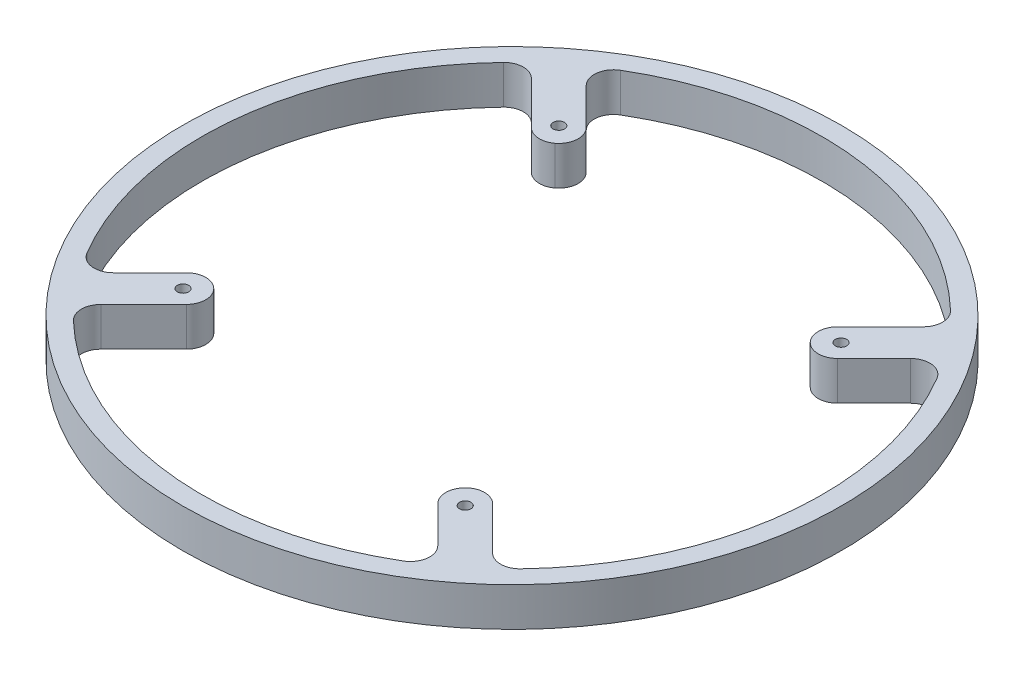
SolidWorks part; units mm, degrees
material "6061-T6 (SS)"
ref_plane "Front Plane" through (0, 0, 0) normal (0, 0, 1) x (1, 0, 0)
ref_plane "Top Plane" through (0, 0, 0) normal (0, 1, 0) x (1, 0, 0)
ref_plane "Right Plane" through (0, 0, 0) normal (1, 0, 0) x (0, 0, -1)
sketch "Sketch2" plane through (0, 0, 0) normal (1, 0, 0) x (0, 0, -1)
  line L0 (-55, 0) -> (-84.9998, 0)
  line L1 (-84.9998, 0) -> (-84.9998, 10)
  line L2 (-84.9998, 10) -> (-55, 10)
  line L5 (-55, 10) -> (-55, 0)
  dimension "D1" = 84.9998
  dimension "D2" = 10
  dimension "D3" = 55
ref_axis "Axis1" through (0, 3.6789, 0) along (0, 1, 0)
revolve "Revolve1" add sketch "Sketch2" angle 360 about axis through (0, 3.6789, 0) along (0, 1, 0)
sketch "Sketch9" plane through (0, 0, 0) normal (0, 1, 0) x (1, 0, 0)
  line L1 (42.4264, -42.4264) -> (-42.4264, -42.4264) construction
  line L2 (42.4264, -42.4264) -> (42.4264, 42.4264) construction
  line L3 (42.4264, 42.4264) -> (-42.4264, 42.4264) construction
  line L4 (-42.4264, -42.4264) -> (-42.4264, 42.4264) construction
  line L5 (0, 0) -> (0, 27.9091) construction
  line L7 (0, 0) -> (26.5726, 0) construction
  line L11 (-43.4619, 48.4619) -> (-36.3909, 55.533) construction
  line L12 (-43.4619, 48.4619) -> (-36.3909, 41.3909) construction
  line L13 (-36.3909, 55.533) -> (-29.3198, 48.4619) construction
  line L16 (-36.3909, 41.3909) -> (-36.3909, 55.533) construction
  line L18 (-43.4619, 48.4619) -> (-29.3198, 48.4619) construction
  line L20 (-29.3198, 48.4619) -> (-36.3909, 41.3909) construction
  point P0 (0, 0)
  point P3 (-42.4264, 42.4264)
  point P355 (-36.3909, 48.4619)
  dimension "D1" = 1.0355
  dimension "D2" = 60
  dimension "D3" = 6.0355
  dimension "D4" = 6.1237
hole_wizard "#32 (0.116) Diameter Hole1" positions "Sketch12" profile "Sketch13" hole size "#32" standard "ANSI Inch" end condition through all
sketch "Sketch12" plane through (0, 0, 0) normal (0, -1, 0) x (-1, 0, 0)
  point P0 (36.3909, 48.4619)
sketch "Sketch13" plane through (-36.3909, 0, -48.4619) normal (1, 0, 0) x (0, 0, -1)
  line L0 (0, 0) -> (0, 10)
  line L1 (0, 10) -> (1.4732, 10)
  line L2 (1.4732, 10) -> (1.4732, 0)
  line L5 (1.4732, 0) -> (0, 0)
  line L11 (0, -6.35) -> (0, 107.95) construction
  dimension "Thru Hole Dia." = 2.9464
  dimension "Thru Hole Depth" = 10
sketch "Sketch14" plane through (0, 0, 0) normal (0, -1, 0) x (1, 0, 0)
  line L0 (0, 0) -> (-36.3909, -48.4619) construction
  line L1 (-33.0708, -38.0708) -> (-54.0132, -59.0132)
  line L2 (-43.9211, 24.779) -> (-65.3239, 46.1818)
  line L3 (0, 0) -> (-48.4619, 36.3909) construction
  line L4 (-43.4619, -48.4619) -> (-36.3909, -41.3909) construction
  line L6 (-41.3909, 36.3909) -> (-48.4619, 29.3198) construction
  line L7 (-41.3909, 36.3909) -> (-48.4619, 43.4619) construction
  line L8 (-48.4619, 43.4619) -> (-55.533, 36.3909) construction
  line L9 (-48.4619, 29.3198) -> (-55.533, 36.3909) construction
  line L10 (-41.3909, 36.3909) -> (-55.533, 36.3909) construction
  line L11 (-48.4619, 43.4619) -> (-48.4619, 29.3198) construction
  line L13 (-43.4619, -48.4619) -> (-36.3909, -55.533) construction
  line L14 (0, 0) -> (26.5726, 0) construction
  arc A0 (-33.0708, -38.0708) -> (-43.9211, 24.779) centre (0, 0) cw
  arc A1 (-65.3239, 46.1818) -> (-54.0132, -59.0132) centre (0, 0) ccw
  circle A2 centre (0, 0) radius 84.9998 construction
  point P14 (-48.4619, 36.3909)
  dimension "D2" = 5
  dimension "D3" = 50.4288
extrude "Cut-Extrude1" cut sketch "Sketch14" against normal through all
pattern_circular "CirPattern1" count 4 over 360 about axis through (0, 3.6789, 0) along (0, 1, 0) of "Cut-Extrude1", "#32 (0.116) Diameter Hole1"
fillet "Fillet1" radius 5 16 edges at (-28.1237, 5, -47.2658) (-36.3104, 5, -41.3104) (-41.3104, 5, 36.3104) (-47.2658, 5, 28.1237) (28.1237, 5, 47.2658) (36.3104, 5, 41.3104) (47.2658, 5, -28.1237) (41.3104, 5, -36.3104) (-59.0132, 5, 54.0132) (46.1818, 5, 65.3239) (-46.1818, 5, -65.3239) (-54.0132, 5, -59.0132) (-65.3239, 5, 46.1818) (54.0132, 5, 59.0132) (65.3239, 5, -46.1818) (59.0132, 5, -54.0132)
